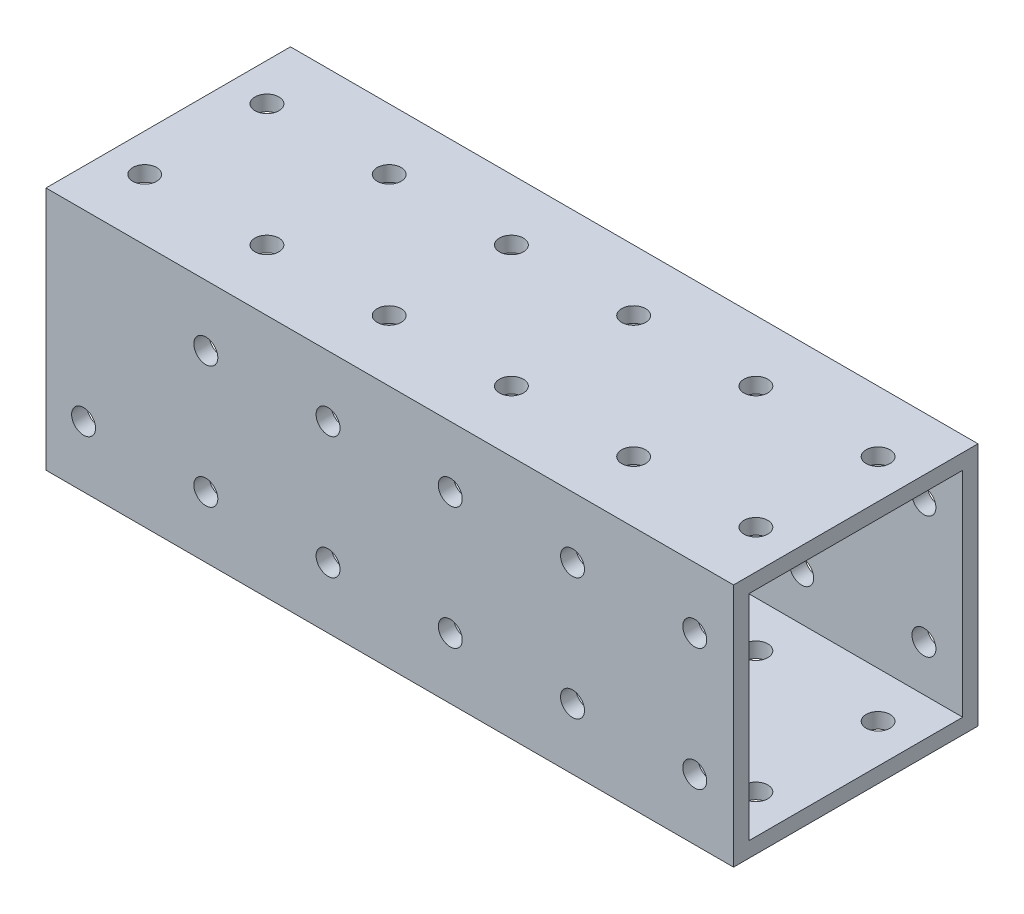
SolidWorks part; units mm, degrees
material "6061-T6 (SS)"
ref_plane "Front Plane" through (0, 0, 0) normal (0, 0, 1) x (1, 0, 0)
ref_plane "Top Plane" through (0, 0, 0) normal (0, 1, 0) x (1, 0, 0)
ref_plane "Right Plane" through (0, 0, 0) normal (1, 0, 0) x (0, 0, -1)
sketch "Sketch1" plane through (0, 0, 0) normal (1, 0, 0) x (0, 0, -1)
  line L1 (0, 0) -> (50.8, 0)
  line L2 (0, 0) -> (0, 50.8)
  line L3 (0, 50.8) -> (50.8, 50.8)
  line L4 (50.8, 0) -> (50.8, 50.8)
  dimension "D1" = 50.8
extrude "Boss-Extrude1" add sketch "Sketch1" along normal blind 142.875
shell "Shell1" thickness 3.175 removed face at (0, 25.4, -25.4) removed face at (142.875, 25.4, -25.4)
sketch "Sketch2" plane through (0, 0, -50.8) normal (0, 0, -1) x (-1, 0, 0)
  circle A0 centre (-134.8133, 38.1) radius 2.4892 construction
  circle A1 centre (-109.4133, 38.1) radius 2.4892 construction
  circle A2 centre (-84.0133, 38.1) radius 2.4892 construction
  circle A3 centre (-58.6133, 38.1) radius 2.4892 construction
  circle A4 centre (-33.2133, 38.1) radius 2.4892 construction
  circle A5 centre (-33.2133, 12.7) radius 2.4892 construction
  circle A6 centre (-58.6133, 12.7) radius 2.4892 construction
  circle A7 centre (-84.0133, 12.7) radius 2.4892 construction
  circle A8 centre (-109.4133, 12.7) radius 2.4892 construction
  circle A9 centre (-134.8133, 12.7) radius 2.4892 construction
  circle A10 centre (-134.8133, 38.1) radius 2.4892
  circle A11 centre (-109.4133, 38.1) radius 2.4892
  circle A12 centre (-84.0133, 38.1) radius 2.4892
  circle A13 centre (-58.6133, 38.1) radius 2.4892
  circle A14 centre (-33.2133, 38.1) radius 2.4892
  circle A15 centre (-33.2133, 12.7) radius 2.4892
  circle A16 centre (-58.6133, 12.7) radius 2.4892
  circle A17 centre (-84.0133, 12.7) radius 2.4892
  circle A18 centre (-109.4133, 12.7) radius 2.4892
  circle A19 centre (-134.8133, 12.7) radius 2.4892
  circle A20 centre (-7.8133, 12.7) radius 2.4892 construction
  circle A21 centre (-7.8133, 12.7) radius 2.4892
extrude "Cut-Extrude1" cut sketch "Sketch2" against normal through all
sketch "Sketch3" plane through (0, 0, 0) normal (0, -1, 0) x (1, 0, 0)
  line L1 (134.8133, -38.1) -> (134.8133, -12.7) construction
  line L2 (134.8133, -12.7) -> (134.8133, 12.7) construction
  line L3 (293.5633, 0) -> (-303.3367, 0) construction
  line L4 (142.875, -50.8) -> (0, -50.8) construction
  circle A0 centre (134.8133, -12.7) radius 2.4892
  circle A1 centre (134.8133, -38.1) radius 2.4892
  dimension "D1" = 4.9784
  dimension "D2" = 12.7
  dimension "D3" = 12.7
extrude "Cut-Extrude2" cut sketch "Sketch3" against normal through all
pattern_linear "LPattern1" count 6 spacing 25.4 along (-1, 0, 0) of "Cut-Extrude2"
